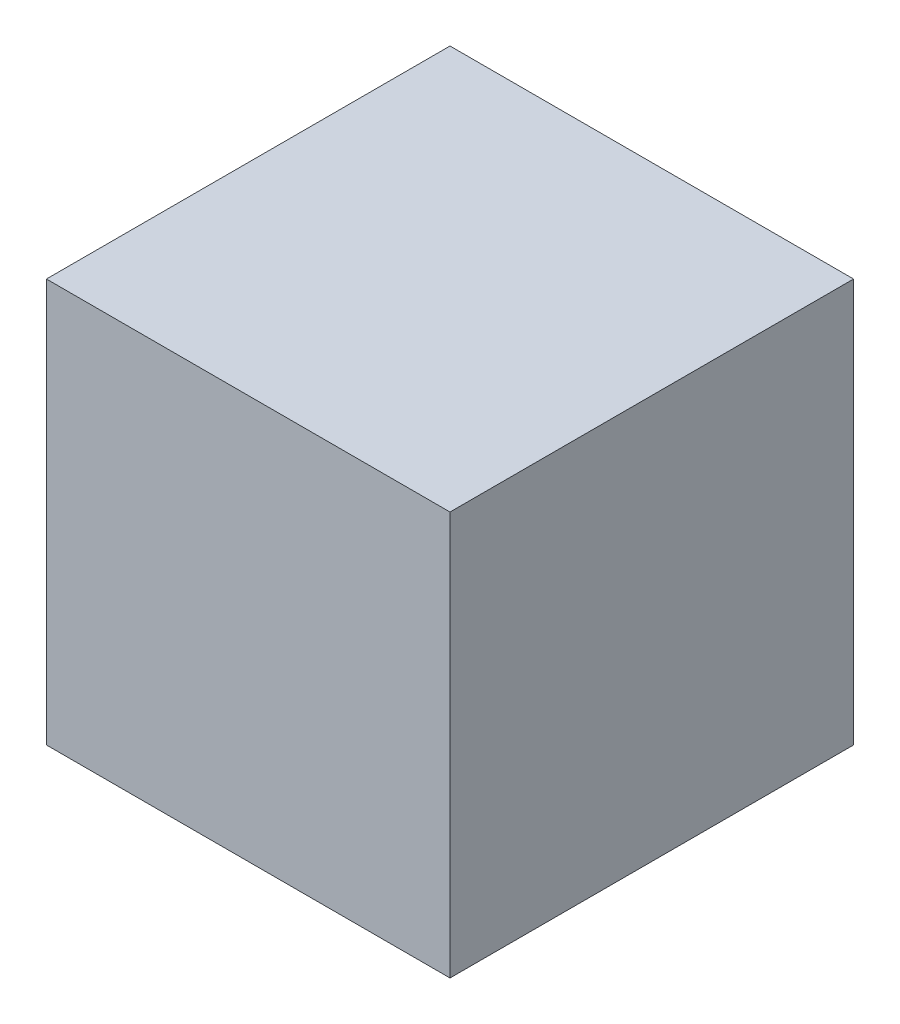
SolidWorks part; units mm, degrees
material "Acier non allié"
ref_plane "Plan de face" through (0, 0, 0) normal (0, 0, 1) x (1, 0, 0)
ref_plane "Plan de dessus" through (0, 0, 0) normal (0, 1, 0) x (1, 0, 0)
ref_plane "Plan de droite" through (0, 0, 0) normal (1, 0, 0) x (0, 0, -1)
sketch "Esquisse1" plane through (0, 0, 0) normal (1, 0, 0) x (0, 0, -1)
  line L0 (4, -4) -> (-4, 4) construction
  line L1 (-4, 4) -> (4, 4)
  line L2 (-4, 4) -> (-4, -4)
  line L3 (-4, -4) -> (4, -4)
  line L4 (4, 4) -> (4, -4)
  line L5 (4, 4) -> (-4, -4) construction
  dimension "D1" = 8
  dimension "D2" = 8
extrude "Boss.-Extru.1" add sketch "Esquisse1" along normal mid plane 8
